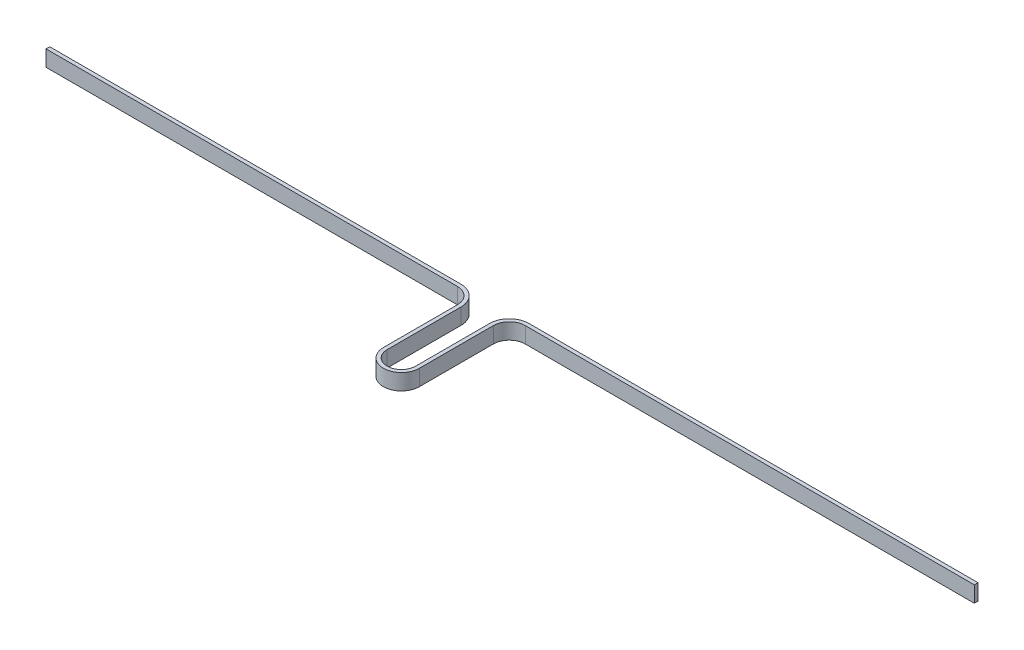
SolidWorks part; units mm, degrees
ref_plane "Front Plane" through (0, 0, 0) normal (0, 0, 1) x (1, 0, 0)
ref_plane "Top Plane" through (0, 0, 0) normal (0, 1, 0) x (1, 0, 0)
ref_plane "Right Plane" through (0, 0, 0) normal (1, 0, 0) x (0, 0, -1)
sketch "Sketch1" plane through (0, 0, 0) normal (0, 1, 0) x (1, 0, 0)
  line L1 (356.75, -267.0175) -> (356.75, -294.7675)
  line L2 (344.01, -294.7675) -> (344.01, -267.0175)
  line L3 (337.64, -260.6475) -> (183.275, -260.6475)
  line L6 (363.12, -260.6475) -> (531.6254, -260.6475)
  arc A0 (356.75, -294.7675) -> (344.01, -294.7675) centre (350.38, -294.7675) cw
  arc A1 (344.01, -267.0175) -> (337.64, -260.6475) centre (337.64, -267.0175) ccw
  arc A2 (363.12, -260.6475) -> (356.75, -267.0175) centre (363.12, -267.0175) ccw
  point P0 (0, 0)
  dimension "D1" = 6.37
  dimension "D2" = 6.37
  dimension "D5" = 168.5054
  dimension "D3" = 6.37
  dimension "D4" = 27.75
  dimension "D7" = 154.365
extrude "Extrude-Thin1" add sketch "Sketch1" along normal blind 6 thin thin type two direction wall 0.376 second wall 1.004
